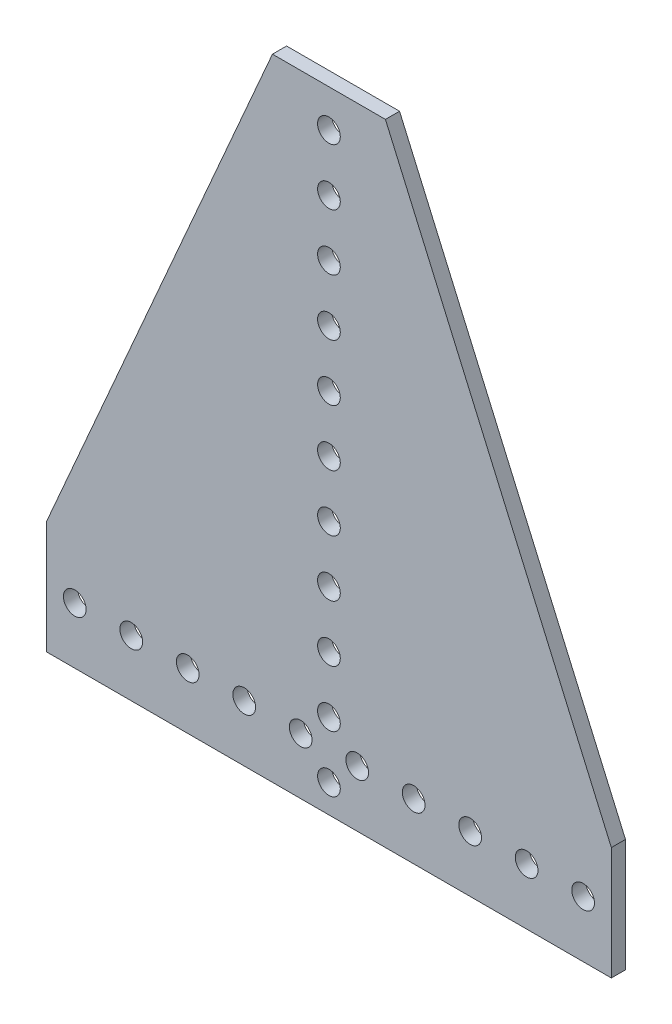
SolidWorks part; units mm, degrees
ref_plane "Front Plane" through (0, 0, 0) normal (0, 0, 1) x (1, 0, 0)
ref_plane "Top Plane" through (0, 0, 0) normal (0, 1, 0) x (1, 0, 0)
ref_plane "Right Plane" through (0, 0, 0) normal (1, 0, 0) x (0, 0, -1)
sketch "Sketch1" plane through (0, 0, 0) normal (0, 0, 1) x (1, 0, 0)
  line L1 (-128, 138.6667) -> (49.8, 138.6667)
  line L2 (-128, 138.6667) -> (-128, -115.3333)
  line L3 (-128, -115.3333) -> (49.8, -115.3333)
  line L4 (49.8, 138.6667) -> (49.8, -115.3333)
  dimension "D1" = 254
  dimension "D2" = 177.8
extrude "Boss-Extrude1" add sketch "Sketch1" along normal blind 3.175
sketch "Sketch2" plane through (0, 0, 3.175) normal (0, 0, 1) x (1, 0, 0)
  line L0 (-39.1, -115.3333) -> (-39.1, 138.6667) construction
  line L1 (-128, -115.3333) -> (49.8, -115.3333) construction
  line L2 (49.8, 138.6667) -> (-128, 138.6667) construction
  line L3 (-39.1, -108.9833) -> (-39.1, -96.2833) construction
  circle A0 centre (-39.1, -108.9833) radius 2.5527
  circle A1 centre (-39.1, -96.2833) radius 2.5527
  circle A2 centre (-39.1, -83.5833) radius 2.5527
  circle A3 centre (-39.1, -70.8833) radius 2.5527
  circle A4 centre (-39.1, -58.1833) radius 2.5527
  circle A5 centre (-39.1, -45.4833) radius 2.5527
  circle A6 centre (-39.1, -32.7833) radius 2.5527
  circle A7 centre (-39.1, -20.0833) radius 2.5527
  circle A8 centre (-39.1, -7.3833) radius 2.5527
  circle A9 centre (-39.1, 5.3167) radius 2.5527
  circle A10 centre (-39.1, 18.0167) radius 2.5527
  circle A11 centre (-39.1, 30.7167) radius 2.5527
  dimension "D1" = 6.35
  dimension "D2" = 5.1054
  dimension "D3" = 12.7
extrude "Cut-Extrude1" cut sketch "Sketch2" against normal through all
sketch "Sketch3" plane through (0, 0, 3.175) normal (0, 0, 1) x (1, 0, 0)
  line L0 (30.75, -102.6333) -> (-17.6342, -102.6333) construction
  line L1 (-128, -115.3333) -> (49.8, -115.3333) construction
  line L2 (49.8, -115.3333) -> (49.8, 138.6667) construction
  line L3 (30.75, -102.6333) -> (18.05, -102.6333) construction
  circle A0 centre (30.75, -102.6333) radius 2.5527
  circle A1 centre (18.05, -102.6333) radius 2.5527
  circle A2 centre (5.35, -102.6333) radius 2.5527
  circle A3 centre (-7.35, -102.6333) radius 2.5527
  circle A4 centre (-20.05, -102.6333) radius 2.5527
  circle A5 centre (-32.75, -102.6333) radius 2.5527
  circle A6 centre (-45.45, -102.6333) radius 2.5527
  circle A7 centre (-58.15, -102.6333) radius 2.5527
  circle A8 centre (-70.85, -102.6333) radius 2.5527
  circle A9 centre (-83.55, -102.6333) radius 2.5527
  circle A10 centre (-96.25, -102.6333) radius 2.5527
  circle A11 centre (-108.95, -102.6333) radius 2.5527
  dimension "D3" = 5.1054
  dimension "D1" = 12.7
  dimension "D2" = 19.05
  dimension "D4" = 12.7
extrude "Cut-Extrude2" cut sketch "Sketch3" against normal through all
sketch "Sketch4" plane through (0, 0, 3.175) normal (0, 0, 1) x (1, 0, 0)
  line L0 (-128, -115.3333) -> (-102.6, -115.3333)
  line L1 (-128, -115.3333) -> (49.8, -115.3333) construction
  line L2 (-102.6, -115.3333) -> (-102.6, -89.9333)
  line L3 (-102.6, -89.9333) -> (-51.8, 26.4641)
  line L4 (-51.8, 26.4641) -> (-26.4, 26.4641)
  line L5 (-26.4, 26.4641) -> (24.4, -89.9333)
  line L6 (24.4, -89.9333) -> (24.4, -115.3333)
  line L7 (24.4, -115.3333) -> (49.8, -115.3333)
  line L8 (49.8, -115.3333) -> (49.8, 138.6667)
  line L9 (49.8, 138.6667) -> (-128, 138.6667)
  line L10 (-128, 138.6667) -> (-128, -115.3333)
  dimension "D1" = 25.4
  dimension "D2" = 25.4
  dimension "D3" = 25.4
  dimension "D4" = 127
  dimension "D5" = 127
  dimension "D6" = 25.4
  dimension "D7" = 25.4
extrude "Cut-Extrude3" cut sketch "Sketch4" against normal through all
